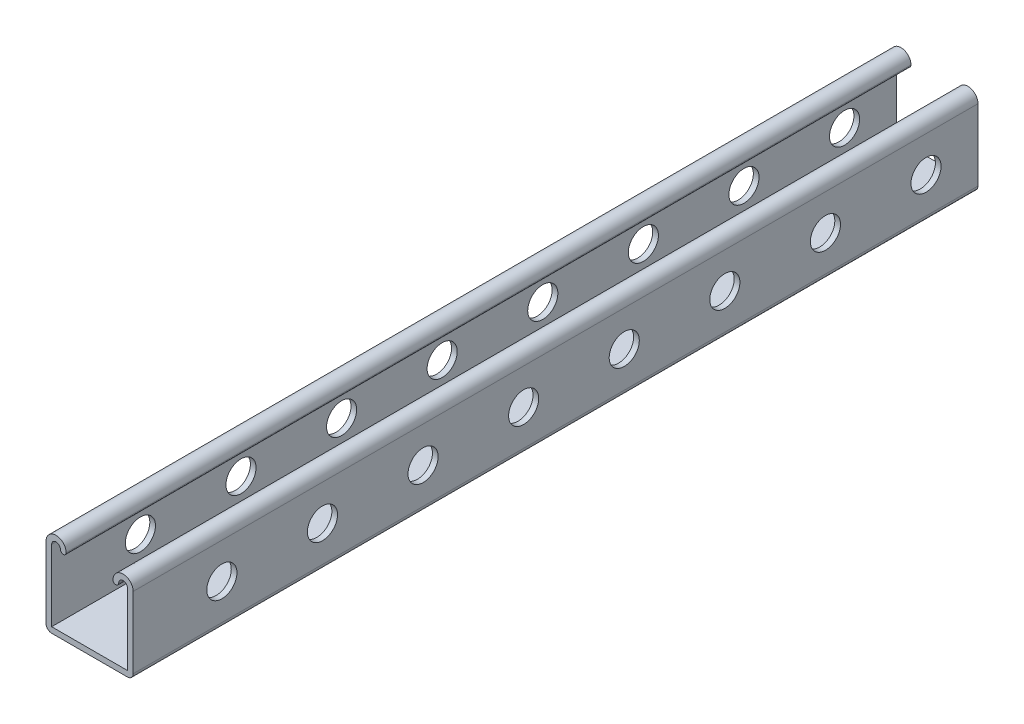
SolidWorks part; units mm, degrees
note: '?' marks a value the reader was unsure of.
material "普通碳钢"
ref_plane "前视基准面" through (0, 0, 0) normal (0, 0, 1) x (1, 0, 0)
ref_plane "上视基准面" through (0, 0, 0) normal (0, 1, 0) x (1, 0, 0)
ref_plane "右视基准面" through (0, 0, 0) normal (1, 0, 0) x (0, 0, -1)
sketch "草图1" plane through (0, 0, 0) normal (0, 0, 1) x (1, 0, 0)
  line L0 (0, 0) -> (35.98, 0)
  line L1 (17.99, 2.6924) -> (17.99, -3.3917) construction
  line L2 (35.98, 2.6924) -> (0, 2.6924)
  line L3 (35.98, 19.6088) -> (0, 19.6088) construction
  line L4 (35.98, 2.6924) -> (35.98, 36.5252)
  line L5 (38.6724, 2.6924) -> (38.6724, 36.5252)
  line L6 (-2.6924, 2.6924) -> (-2.6924, 36.5252)
  line L7 (0, 2.6924) -> (0, 36.5252)
  line L8 (17.99, 19.6088) -> (17.99, 2.6924) construction
  arc A0 (35.98, 0) -> (38.6724, 2.6924) centre (35.98, 2.6924) ccw
  arc A1 (35.98, 36.5252) -> (31.8144, 36.5252) centre (33.8972, 36.5252) ccw
  arc A2 (38.6724, 36.5252) -> (29.122, 36.5252) centre (33.8972, 36.5252) ccw
  arc A3 (29.122, 36.5252) -> (31.8144, 36.5252) centre (30.4682, 36.5252) ccw
  arc A4 (6.858, 36.5252) -> (4.1656, 36.5252) centre (5.5118, 36.5252) cw
  arc A5 (-2.6924, 36.5252) -> (6.858, 36.5252) centre (2.0828, 36.5252) cw
  arc A6 (0, 36.5252) -> (4.1656, 36.5252) centre (2.0828, 36.5252) cw
  arc A7 (0, 0) -> (-2.6924, 2.6924) centre (0, 2.6924) cw
  point P25 (17.99, 19.6088)
extrude "凸台-拉伸1" add sketch "草图1" along normal blind 401.066
ref_plane "基准面1" through (-2.6924, 0, 0) normal (-1, 0, 0) x (0, 0, 1)
sketch "草图2" plane through (-2.6924, 0, 0) normal (-1, 0, 0) x (0, 0, 1)
  line L0 (0, 19.6088) -> (17.526, 19.6088) construction
  line L1 (0, 36.5252) -> (0, 2.6924) construction
  line L2 (17.526, 19.6088) -> (31.8262, 19.6088) construction
  circle A0 centre (24.6761, 19.6088) radius 7.1501
extrude "切除-拉伸1" cut sketch "草图2" against normal blind 5.08
pattern_linear "阵列(线性)1" count 8 spacing 47.752 along (0, 0, 1) of "切除-拉伸1"
ref_axis "基准轴3" through (17.99, 19.6088, 0) along (0, 0, -1)?
pattern_circular "阵列(圆周)2" count 3 every 90 about axis through (17.99, 19.6088, 0) along (0, 0, -1) of "切除-拉伸1", "阵列(线性)1"
